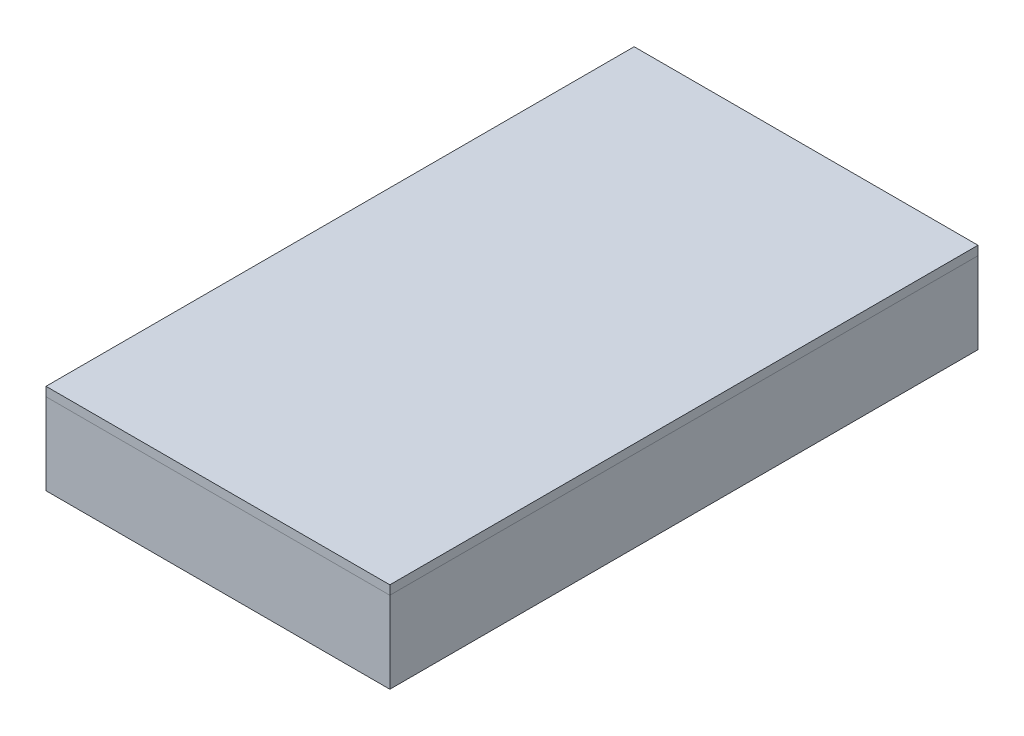
SolidWorks part; units mm, degrees
note: The reader was unsure of these and kept them because the rebuilt part matched: shared geometry of "Sketch3<3>", "Sketch6<3>".
ref_plane "Front Plane" through (0, 0, 0) normal (0, 0, 1) x (1, 0, 0)
ref_plane "Top Plane" through (0, 0, 0) normal (0, 1, 0) x (1, 0, 0)
ref_plane "Right Plane" through (0, 0, 0) normal (1, 0, 0) x (0, 0, -1)
sketch "Sketch2" plane through (0, 0, 0) normal (0, 1, 0) x (1, 0, 0)
  line L0 (9.3918, 23) -> (12.6392, 30.6504) construction
  line L1 (8.0012, 23) -> (11.3715, 30.9397) construction
  line L2 (-17.4418, -23.5727) -> (-14.5634, 23.4884) construction
  line L3 (14.5634, -23.4884) -> (17.4418, 23.5727) construction
  line L4 (-6.5783, 31) -> (10.4548, 31) construction
  line L5 (-10.4548, -31) -> (6.5783, -31) construction
  line L6 (-6.5783, 23) -> (9.3918, 23) construction
  line L7 (-9.3918, -23) -> (6.5783, -23) construction
  line L8 (-9.3918, -23) -> (-8.2297, -4) construction
  line L9 (9.3333, 22.0431) -> (12.9414, 30.5435) construction
  line L10 (6.5783, -23) -> (9.2488, -30.5411) construction
  line L11 (6.5783, -23) -> (7.7404, -4) construction
  line L12 (-7.7404, 4) -> (8.2297, 4) construction
  line L13 (-8.2297, -4) -> (7.7404, -4) construction
  line L14 (-6.5783, 23) -> (-12.0598, 28.827) construction
  line L15 (8.2297, 4) -> (9.3918, 23) construction
  line L16 (5.2204, -23) -> (8.0078, -30.8713) construction
  line L17 (-7.7404, 4) -> (-6.5783, 23) construction
  line L18 (-9.3918, -23) -> (-18.0557, -31.1502) construction
  line L19 (-11.4496, 29.3459) -> (-5.48, 23) construction
  line L20 (-12.615, 28.2496) -> (-6.6454, 21.9037) construction
  line L21 (-14.9719, -29.3476) -> (-8.2242, -23) construction
  line L22 (-16.0682, -28.1822) -> (-9.3205, -21.8346) construction
  line L23 (6.6283, -22.1826) -> (9.5483, -30.4283) construction
  line L24 (-11.6, 0) -> (-6.2918, 4) construction
  line L25 (-11.6, 0) -> (-6.2918, -4) construction
  line L26 (11.6, 0) -> (6.2918, 4) construction
  line L27 (11.6, 0) -> (6.2918, -4) construction
  line L28 (-7.6819, 4.9559) -> (-12.9293, 1.0017) construction
  line L29 (-12.9293, 1.0017) -> (-15.8061, 3.1696) construction
  line L30 (-16.2126, -3.4758) -> (-12.9293, -1.0017) construction
  line L31 (-12.9293, -1.0017) -> (-8.2615, -4.5192) construction
  line L32 (7.6819, -4.9559) -> (12.9293, -1.0017) construction
  line L33 (12.9293, -1.0017) -> (15.8061, -3.1696) construction
  line L34 (8.2615, 4.5192) -> (12.9293, 1.0017) construction
  line L35 (12.9293, 1.0017) -> (16.2126, 3.4758) construction
  line L36 (-19, -32.5) -> (-19, 32.5) construction
  line L37 (19, -32.5) -> (19, 32.5) construction
  line L38 (-19, 32.5) -> (19, 32.5) construction
  line L39 (-19, -32.5) -> (19, -32.5) construction
  line L40 (-16.8257, -13.5) -> (15.1743, -13.5) construction
  line L41 (-15.1743, 13.5) -> (16.8257, 13.5) construction
  line L42 (16.7794, 27) -> (-13.5065, 27) construction
  line L43 (-10.4548, -31) -> (13.8794, -31) construction
  line L44 (13.5065, -27) -> (-16.7794, -27) construction
  line L45 (10.1479, -30.1595) -> (13.8353, 30.1296) construction
  line L46 (-10.1479, 30.1595) -> (-13.8353, -30.1296) construction
  line L47 (-1.896, -31) -> (1.896, 31) construction
  arc A0 (-6.5783, 31) -> (-14.5634, 23.4884) centre (-6.5783, 23) ccw construction
  arc A1 (14.5634, -23.4884) -> (6.5783, -31) centre (6.5783, -23) cw construction
  arc A2 (17.4418, 23.5727) -> (10.4548, 31) centre (10.4548, 24) ccw construction
  arc A3 (-10.4548, -31) -> (-17.4418, -23.5727) centre (-10.4548, -24) cw construction
  point P0 (-16, 0)
  point P3 (-16, 0)
  point P8 (16, 0)
  point P42 (-11.6, 0)
  point P43 (11.6, 0)
  point P67 (7.1594, -13.5)
  point P70 (-7.1594, 13.5)
  point P72 (1.9383, 31)
  point P85 (1.6364, 27)
  point P86 (-12.8182, -13.5)
  point P87 (-11.1668, 13.5)
  point P88 (-1.6364, -27)
  point P89 (12.8182, 13.5)
  point P90 (11.1668, -13.5)
  dimension "D6" = 8
  dimension "D8" = 7
  dimension "D3" = 86.5
  dimension "D5" = 16
  dimension "D4" = 16
  dimension "D7" = 8
  dimension "D11" = 0.8
  dimension "D12" = 0.8
  dimension "D13" = 0.8
  dimension "D14" = 0.8
  dimension "D9" = 4
  dimension "D10" = 4
  dimension "D2" = 31
  dimension "D15" = 31
  dimension "D16" = 113
  dimension "D17" = 1.6
  dimension "D18" = 0.32
  dimension "D19" = 109.5
  dimension "D20" = 1.6
  dimension "D21" = 0.32
  dimension "D22" = 4.4
  dimension "D23" = 143
  dimension "D24" = 4.4
  dimension "D25" = 143
  dimension "D26" = 1.6
  dimension "D27" = 1.6
  dimension "D28" = 1.6
  dimension "D29" = 1.6
  dimension "D32" = 1.5
  dimension "D33" = 1.5
  dimension "D34" = 4
  dimension "D35" = 4
  dimension "D36" = 4
  dimension "D37" = 4
  dimension "D30" = 19
  dimension "D31" = 19
sketch "Sketch3" plane through (0, 0, 0) normal (0, 1, 0) x (1, 0, 0)
  line L0 (-15.8061, 3.1696) -> (-14.5634, 23.4884)
  line L1 (-15.8061, 3.1696) -> (-12.9293, 1.0017)
  line L2 (-12.9293, 1.0017) -> (-7.6819, 4.9559)
  line L3 (-7.6819, 4.9559) -> (-6.6454, 21.9037)
  line L4 (-6.6454, 21.9037) -> (-12.615, 28.2496)
  line L5 (-11.4496, 29.3459) -> (-5.48, 23)
  line L6 (-5.48, 23) -> (8.0012, 23)
  line L7 (8.0012, 23) -> (11.3715, 30.9397)
  line L8 (-6.5783, 31) -> (10.4548, 31)
  line L9 (-11.6, 0) -> (-6.2918, 4)
  line L10 (-6.2918, 4) -> (6.2918, 4)
  line L11 (6.2918, 4) -> (11.6, 0)
  line L12 (11.6, 0) -> (6.2918, -4)
  line L13 (6.2918, -4) -> (-6.2918, -4)
  line L14 (-6.2918, -4) -> (-11.6, 0)
  line L15 (9.3333, 22.0431) -> (12.9414, 30.5435)
  line L16 (9.3333, 22.0431) -> (8.2615, 4.5192)
  line L17 (8.2615, 4.5192) -> (12.9293, 1.0017)
  line L18 (12.9293, 1.0017) -> (16.2126, 3.4758)
  line L19 (16.2126, 3.4758) -> (17.4418, 23.5727)
  line L20 (6.6283, -22.1826) -> (7.6819, -4.9559)
  line L21 (7.6819, -4.9559) -> (12.9293, -1.0017)
  line L22 (12.9293, -1.0017) -> (15.8061, -3.1696)
  line L23 (15.8061, -3.1696) -> (14.5634, -23.4884)
  line L24 (6.6283, -22.1826) -> (9.5483, -30.4283)
  line L25 (8.0078, -30.8713) -> (5.2204, -23)
  line L26 (5.2204, -23) -> (-8.2242, -23)
  line L27 (-8.2242, -23) -> (-14.9719, -29.3476)
  line L28 (-16.0682, -28.1822) -> (-9.3205, -21.8346)
  line L29 (-9.3205, -21.8346) -> (-8.2615, -4.5192)
  line L30 (-8.2615, -4.5192) -> (-12.9293, -1.0017)
  line L31 (-12.9293, -1.0017) -> (-16.2126, -3.4758)
  line L32 (-16.2126, -3.4758) -> (-17.4418, -23.5727)
  line L33 (-10.4548, -31) -> (6.5783, -31)
  line L34 (-19, 32.5) -> (19, 32.5)
  line L35 (19, 32.5) -> (19, -32.5)
  line L36 (19, -32.5) -> (-19, -32.5)
  line L37 (-19, -32.5) -> (-19, 32.5)
  arc A0 (-14.5634, 23.4884) -> (-12.615, 28.2496) centre (-6.5783, 23) cw
  arc A1 (-11.4496, 29.3459) -> (-6.5783, 31) centre (-6.5783, 23) cw
  arc A2 (10.4548, 31) -> (11.3715, 30.9397) centre (10.4548, 24) cw
  arc A3 (12.9414, 30.5435) -> (17.4418, 23.5727) centre (10.4548, 24) cw
  arc A5 (9.5483, -30.4283) -> (14.5634, -23.4884) centre (6.5783, -23) ccw
  arc A6 (8.0078, -30.8713) -> (6.5783, -31) centre (6.5783, -23) cw
  arc A7 (-10.4548, -31) -> (-14.9719, -29.3476) centre (-10.4548, -24) cw
  arc A8 (-16.0682, -28.1822) -> (-17.4418, -23.5727) centre (-10.4548, -24) cw
extrude "Boss-Extrude1" add sketch "Sketch3" against normal blind 0.64 contours L37 L36 L35 L34 A5 L24 L20 L21 L22 L23 L13 L14 L9 L10 L11 L12 L0 A0 L4 L3 L2 L1 L8 A2 L7 L6 L5 A1 L15 A3 L19 L18 L17 L16 L33 A7 L27 L26 L25 A6 L28 A8 L32 L31 | A0 L0 L1 L2 L3 L4 | A2 L8 A1 L5 L6 L7 | A3 L15 L16 L17 L18 L19 | L14 L13 L12 L11 L10 L9 | A8 L28 L29 L30 L31 L32 | A7 L33 A6 L25 L26 L27 | L24 A5 L23 L22 L21 L20
extrude "Boss-Extrude2" add sketch "Sketch3<3>" against normal blind 10
sketch "Sketch3<3>" plane through (0, 0, 0) normal (0, 1, 0) x (1, 0, 0) same geometry as "Sketch3"
ref_plane "Plane1" through (0, -1, 0) normal (0, 1, 0) x (1, 0, 0)
split "Split1" trim tools "Plane1" bodies to split 110 resulting bodies 112 113
sketch "Sketch6" plane through (0, 0, 0) normal (0, 1, 0) x (1, 0, 0)
  line L0 (-15.1743, 13.5) -> (16.8257, 13.5) construction
  line L1 (-16.8257, -13.5) -> (15.1743, -13.5) construction
  circle A0 centre (0.8257, 13.5) radius 2.5
  circle A1 centre (-0.8257, -13.5) radius 2.5
  circle A2 centre (0.8257, 13.5) radius 2.6
  circle A3 centre (-0.8257, -13.5) radius 2.6
  dimension "D1" = 5
  dimension "D2" = 0.1
extrude "Boss-Extrude3" add sketch "Sketch6" against normal blind 3 contours A0 | A1
extrude "Cut-Extrude2" cut sketch "Sketch6<3>" against normal blind 4 contours A0 | A2 A0 | A1 | A3 A1
sketch "Sketch6<3>" plane through (0, 0, 0) normal (0, 1, 0) x (1, 0, 0) same geometry as "Sketch6"
sketch "Sketch4" plane through (0, 0, 0) normal (0, 1, 0) x (1, 0, 0)
  line L1 (-0.8636, 29.5) -> (4.1364, 29.5)
  line L2 (-0.8636, 29.5) -> (-0.8636, 24.5)
  line L3 (-0.8636, 24.5) -> (4.1364, 24.5)
  line L4 (4.1364, 29.5) -> (4.1364, 24.5)
  line L5 (-0.8636, 29.5) -> (4.1364, 24.5) construction
  line L6 (-0.8636, 24.5) -> (4.1364, 29.5) construction
  line L7 (10.3182, 16) -> (15.3182, 16)
  line L8 (10.3182, 16) -> (10.3182, 11)
  line L9 (10.3182, 11) -> (15.3182, 11)
  line L10 (15.3182, 16) -> (15.3182, 11)
  line L11 (10.3182, 16) -> (15.3182, 11) construction
  line L12 (10.3182, 11) -> (15.3182, 16) construction
  line L13 (-2.5, 2.5) -> (2.5, 2.5)
  line L14 (-2.5, 2.5) -> (-2.5, -2.5)
  line L15 (-2.5, -2.5) -> (2.5, -2.5)
  line L16 (2.5, 2.5) -> (2.5, -2.5)
  line L17 (-2.5, 2.5) -> (2.5, -2.5) construction
  line L18 (-2.5, -2.5) -> (2.5, 2.5) construction
  line L19 (-13.6668, 16) -> (-8.6668, 16)
  line L20 (-13.6668, 16) -> (-13.6668, 11)
  line L21 (-13.6668, 11) -> (-8.6668, 11)
  line L22 (-8.6668, 16) -> (-8.6668, 11)
  line L23 (-13.6668, 16) -> (-8.6668, 11) construction
  line L24 (-13.6668, 11) -> (-8.6668, 16) construction
  line L25 (-15.3182, -11) -> (-10.3182, -11)
  line L26 (-15.3182, -11) -> (-15.3182, -16)
  line L27 (-15.3182, -16) -> (-10.3182, -16)
  line L28 (-10.3182, -11) -> (-10.3182, -16)
  line L29 (-15.3182, -11) -> (-10.3182, -16) construction
  line L30 (-15.3182, -16) -> (-10.3182, -11) construction
  line L31 (-4.1364, -29.5) -> (0.8636, -29.5)
  line L32 (-4.1364, -29.5) -> (-4.1364, -24.5)
  line L33 (-4.1364, -24.5) -> (0.8636, -24.5)
  line L34 (0.8636, -29.5) -> (0.8636, -24.5)
  line L35 (-4.1364, -29.5) -> (0.8636, -24.5) construction
  line L36 (-4.1364, -24.5) -> (0.8636, -29.5) construction
  line L37 (8.6668, -16) -> (13.6668, -16)
  line L38 (8.6668, -16) -> (8.6668, -11)
  line L39 (8.6668, -11) -> (13.6668, -11)
  line L40 (13.6668, -16) -> (13.6668, -11)
  line L41 (8.6668, -16) -> (13.6668, -11) construction
  line L42 (8.6668, -11) -> (13.6668, -16) construction
  point P0 (1.6364, 27)
  point P6 (12.8182, 13.5)
  point P12 (0, 0)
  point P18 (-11.1668, 13.5)
  point P24 (-12.8182, -13.5)
  point P30 (-1.6364, -27)
  point P36 (11.1668, -13.5)
  dimension "D1" = 5
  dimension "D2" = 27
  dimension "D3" = 27
  dimension "D4" = 13.5
  dimension "D5" = 13.5
  dimension "D6" = 1.6364
  dimension "D7" = 1.6364
  dimension "D8" = 12.8182
  dimension "D9" = 11.1668
  dimension "D10" = 12.8182
  dimension "D11" = 11.1668
sketch "Sketch5" plane through (0, 0, 0) normal (0, 1, 0) x (1, 0, 0)
  line L0 (-19, 32.5) -> (19, 32.5) construction
  line L1 (-19, -32.5) -> (-19, 32.5) construction
  line L2 (19, -32.5) -> (19, 32.5) construction
  line L3 (-19, -32.5) -> (19, -32.5) construction
  circle A0 centre (-16, 29.5) radius 1.45
  circle A1 centre (16, -29.5) radius 1.45
  dimension "D1" = 2.9
  dimension "D4" = 3
  dimension "D5" = 3
  dimension "D6" = 16
  dimension "D7" = 29.5
  dimension "D8" = 29.5
  dimension "D9" = 16
extrude "Cut-Extrude1" cut sketch "Sketch5" along normal blind 6 from surface at -10 starting at face at (-13.4404, -10, 13.7846)
equation "\"D4@Sketch2\"=\"D5@Sketch2\""
equation "\"D7@Sketch2\"=\"D6@Sketch2\""
equation "\"D11@Sketch2\"=\"D6@Sketch2\"/10"
equation "\"D12@Sketch2\"=\"D11@Sketch2\""
equation "\"D13@Sketch2\"=\"D11@Sketch2\""
equation "\"D14@Sketch2\"=\"D13@Sketch2\""
equation "\"D9@Sketch2\"=\"D6@Sketch2\"/2"
equation "\"D10@Sketch2\"=\"D9@Sketch2\""
equation "\"D15@Sketch2\"=\"D2@Sketch2\""
equation "\"D17@Sketch2\"=\"D12@Sketch2\"*2"
equation "\"D18@Sketch2\"=\"D17@Sketch2\"/5"
equation "\"D19@Sketch2\"=\"D16@Sketch2\"-(90-\"D3@Sketch2\")"
equation "\"D20@Sketch2\"=\"D17@Sketch2\""
equation "\"D21@Sketch2\"=\"D18@Sketch2\""
equation "\"D22@Sketch2\"=\"D6@Sketch2\"*0.55"
equation "\"D24@Sketch2\"=\"D22@Sketch2\""
equation "\"D25@Sketch2\"=\"D23@Sketch2\""
equation "\"D26@Sketch2\"=\"D17@Sketch2\""
equation "\"D27@Sketch2\"=\"D26@Sketch2\""
equation "\"D28@Sketch2\"=\"D27@Sketch2\""
equation "\"D29@Sketch2\"=\"D28@Sketch2\""
equation "\"D33@Sketch2\"=\"D32@Sketch2\""
equation "\"D34@Sketch2\"=\"D6@Sketch2\"/2"
equation "\"D35@Sketch2\"=\"D34@Sketch2\""
equation "\"D36@Sketch2\"=\"D34@Sketch2\""
equation "\"D37@Sketch2\"=\"D34@Sketch2\""
equation "\"D31@Sketch2\"=\"D30@Sketch2\""
equation "\"D3@Sketch5\"=\"D2@Sketch5\""
equation "\"D4@Sketch5\"=\"D2@Sketch5\""
equation "\"D5@Sketch5\"=\"D4@Sketch5\""
